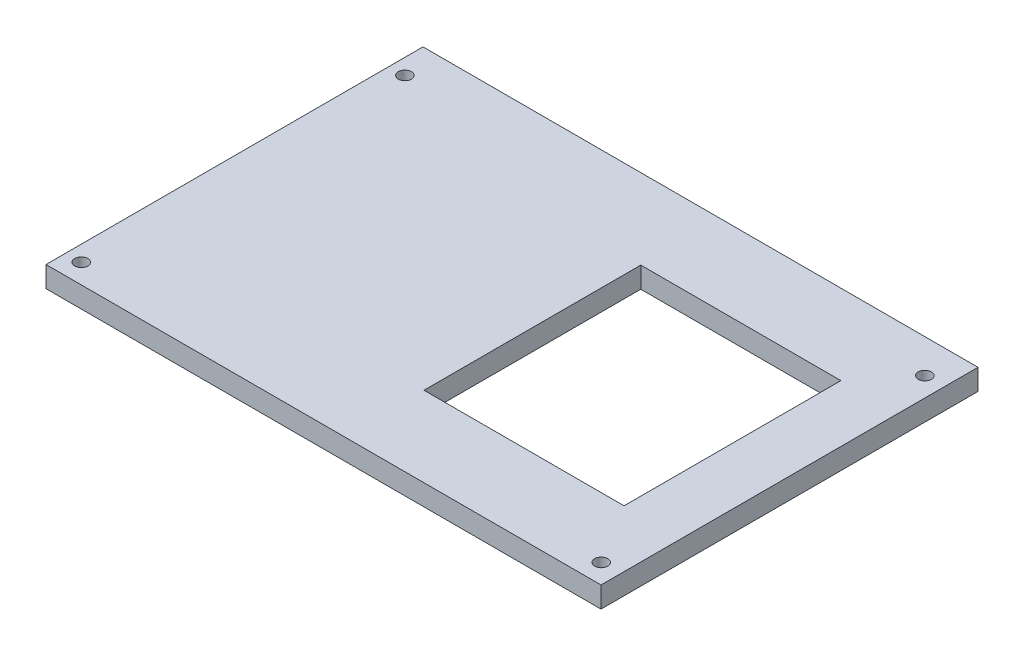
SolidWorks part; units mm, degrees
ref_plane "Front Plane" through (0, 0, 0) normal (0, 0, 1) x (1, 0, 0)
ref_plane "Top Plane" through (0, 0, 0) normal (0, 1, 0) x (1, 0, 0)
ref_plane "Right Plane" through (0, 0, 0) normal (1, 0, 0) x (0, 0, -1)
sketch "Sketch2" plane through (0, 0, 0) normal (0, 0, 1) x (1, 0, 0)
  line L1 (-53, 2) -> (53, 2)
  line L2 (-53, 2) -> (-53, -2)
  line L3 (-53, -2) -> (53, -2)
  line L4 (53, 2) -> (53, -2)
  line L5 (-53, 2) -> (53, -2) construction
  line L6 (-53, -2) -> (53, 2) construction
  point P0 (0, 0)
  dimension "D1" = 106
  dimension "D2" = 4
extrude "Boss-Extrude1" add sketch "Sketch2" along normal blind 72
sketch "Sketch4" plane through (0, 2, 0) normal (0, 1, 0) x (1, 0, 0)
  line L0 (-53, -72) -> (53, -72) construction
  line L1 (53, -72) -> (53, 0) construction
  line L2 (-62.6793, -72) -> (-62.6793, -4) construction
  line L3 (-50.0049, -4) -> (-53, -4) construction
  line L4 (-53, -72) -> (-53, 0) construction
  line L5 (-53, -4) -> (53, -4) construction
  line L6 (-56.8726, -4) -> (-56.8726, -6.4507) construction
  line L7 (-55.3882, -72) -> (-55.3882, -68.2507) construction
  line L8 (53, -77.5021) -> (49.2951, -77.5021) construction
  line L9 (53, 3.1613) -> (49.2951, 3.1613) construction
  line L10 (-53.7098, 3.1613) -> (-50.0049, 3.1613) construction
  line L11 (-53, -36) -> (53, -36) construction
  line L12 (0, 0) -> (0, -72) construction
  line L13 (53, 0) -> (-53, 0) construction
  circle A0 centre (-50.0049, -68.2507) radius 1.25
  circle A1 centre (49.2951, -68.2507) radius 1.25
  circle A2 centre (49.2951, -6.4507) radius 1.25
  circle A3 centre (-50.0049, -6.4507) radius 1.25
  dimension "D6" = 2.5
  dimension "D1" = 106
  dimension "D2" = 72
  dimension "D3" = 68
  dimension "D4" = 99.3
  dimension "D5" = 61.8
extrude "Cut-Extrude1" cut sketch "Sketch4" against normal through all contours A3 | A0 | A1 | A2 region at (-50.0049, 2, 68.2507) region at (49.2951, 2, 68.2507) region at (49.2951, 2, 6.4507) region at (-50.0049, 2, 6.4507)
sketch "Sketch5" plane through (0, 0, 0) normal (0, 0, -1) x (-1, 0, 0)
  line L0 (-53, 0) -> (53, 0) construction
  line L1 (-53, -2) -> (-53, 2) construction
  line L2 (53, 2) -> (53, -2) construction
  circle A0 centre (0, 0) radius 1.75
  circle A1 centre (26.5, 0) radius 1.75
  circle A2 centre (-26.5, 0) radius 1.75
  dimension "D3" = 3.5
  dimension "D1" = 26.5
  dimension "D2" = 26.5
extrude "Cut-Extrude2" cut sketch "Sketch5" against normal blind 10
sketch "Sketch6" plane through (0, 2, 0) normal (0, 1, 0) x (1, 0, 0)
  line L0 (0, 0) -> (0, -72) construction
  line L1 (53, -72) -> (-53, -72) construction
  line L2 (-53, -36) -> (53, -36) construction
  line L3 (-53, -72) -> (-53, 0) construction
  line L4 (53, -72) -> (53, 0) construction
  line L6 (3.8895, -15.2958) -> (42.1105, -15.2958)
  line L7 (3.8895, -15.2958) -> (3.8895, -56.7042)
  line L8 (3.8895, -56.7042) -> (42.1105, -56.7042)
  line L9 (42.1105, -15.2958) -> (42.1105, -56.7042)
  line L10 (3.8895, -15.2958) -> (42.1105, -56.7042) construction
  line L11 (3.8895, -56.7042) -> (42.1105, -15.2958) construction
  point P11 (23, -36)
  dimension "D1" = 23
  dimension "D2" = 30
extrude "Cut-Extrude3" cut sketch "Sketch6" against normal blind 10
